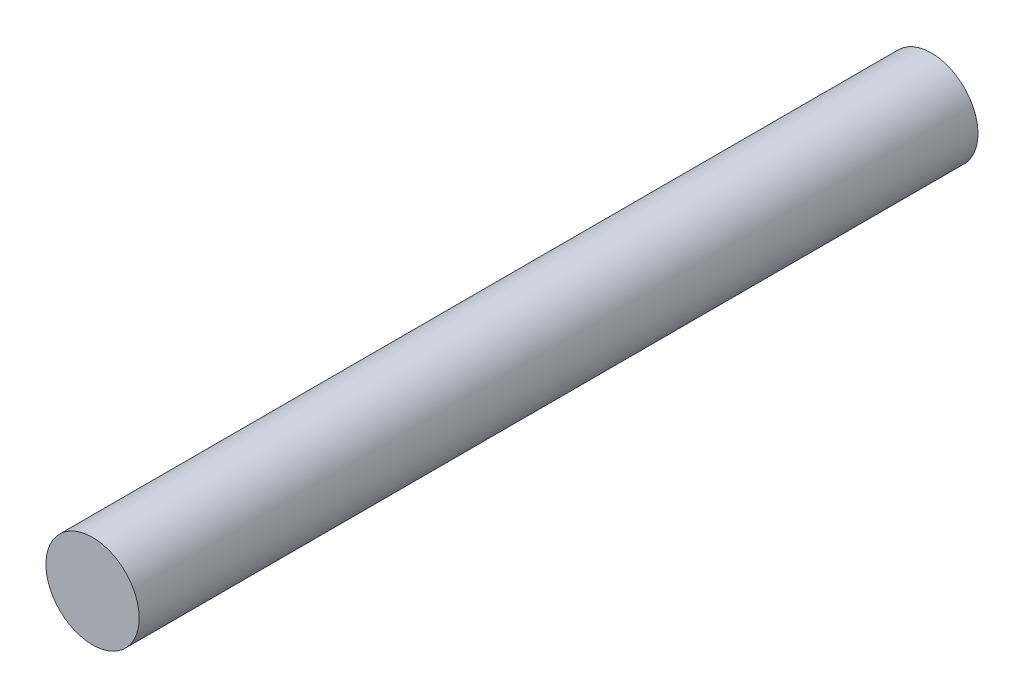
SolidWorks part; units mm, degrees
material "6061-T6 (SS)"
ref_plane "Front" through (0, 0, 0) normal (0, 0, 1) x (1, 0, 0)
ref_plane "Top" through (0, 0, 0) normal (0, 1, 0) x (1, 0, 0)
ref_plane "Right" through (0, 0, 0) normal (1, 0, 0) x (0, 0, -1)
sketch "Sketch1" plane through (0, 0, 0) normal (0, 0, 1) x (1, 0, 0)
  circle A0 centre (0, 0) radius 3.175
  dimension "D1" = 6.35
extrude "Boss-Extrude1" add sketch "Sketch1" along normal blind 57.15
